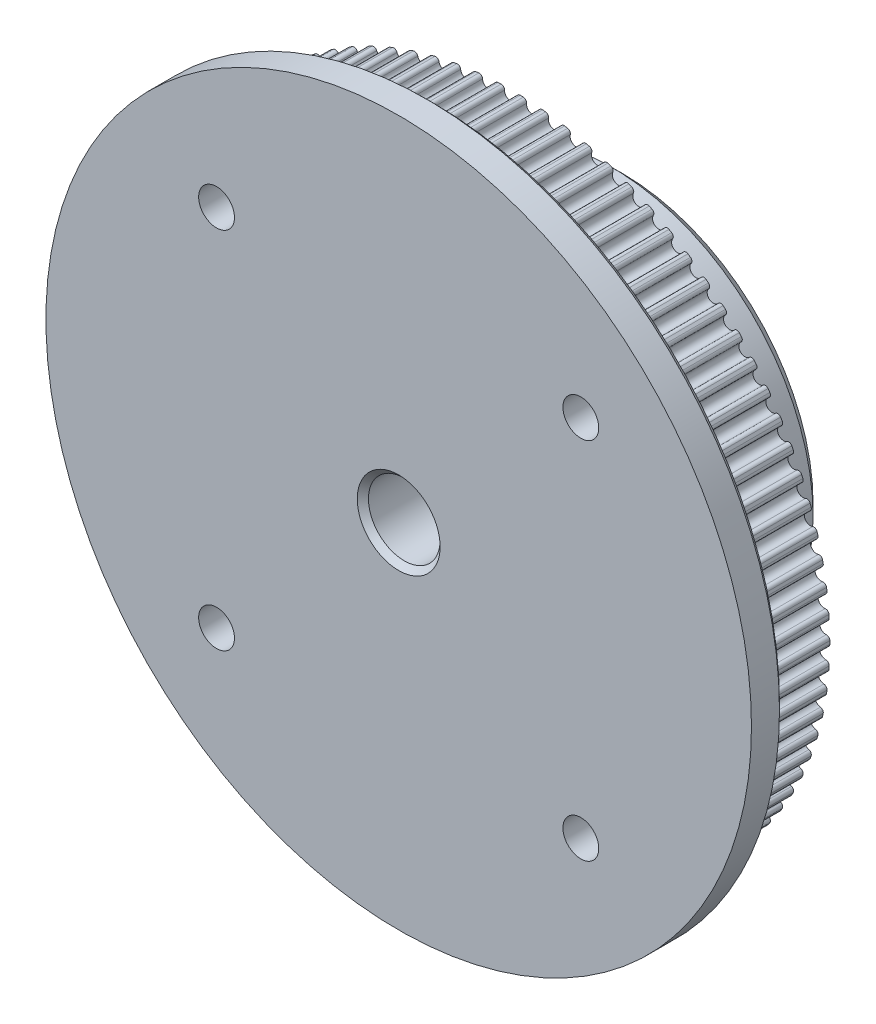
SolidWorks part; units mm, degrees
ref_plane "Спереди" through (0, 0, 0) normal (0, 0, 1) x (1, 0, 0)
ref_plane "Сверху" through (0, 0, 0) normal (0, 1, 0) x (1, 0, 0)
ref_plane "Справа" through (0, 0, 0) normal (1, 0, 0) x (0, 0, -1)
sketch "Эскиз2" plane through (0, 0, 0) normal (1, 0, 0) x (0, 0, -1)
  line L0 (0, 0) -> (0, 31.5)
  line L1 (0, 31.5) -> (3, 31.5)
  line L2 (3, 31.5) -> (3, 28.5)
  line L3 (3, 28.5) -> (10, 28.5)
  line L4 (0, 0) -> (10, 0)
  line L5 (10, 28.5) -> (10, 0)
  dimension "D1" = 3
  dimension "D2" = 7
  dimension "D3" = 28.5
  dimension "D4" = 3
revolve "Повернуть1" add sketch "Эскиз2" angle 360 about L4
sketch "Эскиз5" plane through (0, 0, 0) normal (0, 0, 1) x (1, 0, 0)
  line L1 (0, 0) -> (28.5, 0) construction
  circle A1 centre (0, 0) radius 28.5 construction
  circle A3 centre (0, 0) radius 28.5 construction
sketch "Эскиз7" plane through (0, 0, -10) normal (0, 0, -1) x (-1, 0, 0)
  line L0 (0, 0) -> (0, 28.5) construction
  line L1 (-1.9636, 28.0814) -> (0, 0) construction
  circle A0 centre (0, 0) radius 28.5 construction
  circle A1 centre (0, 28.15) radius 0.55
  circle A2 centre (0, 0) radius 28.5 construction
  circle A3 centre (0, 0) radius 28.5 construction
  circle A4 centre (1.9636, 28.0814) radius 0.55
  circle A5 centre (3.9177, 27.876) radius 0.55
  circle A6 centre (5.8527, 27.5349) radius 0.55
  circle A7 centre (7.7592, 27.0595) radius 0.55
  circle A8 centre (9.6279, 26.4523) radius 0.55
  circle A9 centre (11.4496, 25.7163) radius 0.55
  circle A10 centre (13.2156, 24.855) radius 0.55
  circle A11 centre (14.9172, 23.8726) radius 0.55
  circle A12 centre (16.5462, 22.7738) radius 0.55
  circle A13 centre (18.0945, 21.5642) radius 0.55
  circle A14 centre (19.5546, 20.2494) radius 0.55
  circle A15 centre (20.9195, 18.836) radius 0.55
  circle A16 centre (22.1825, 17.3309) radius 0.55
  circle A17 centre (23.3374, 15.7413) radius 0.55
  circle A18 centre (24.3786, 14.075) radius 0.55
  circle A19 centre (25.3011, 12.3401) radius 0.55
  circle A20 centre (26.1002, 10.5452) radius 0.55
  circle A21 centre (26.7722, 8.6988) radius 0.55
  circle A22 centre (27.3138, 6.8101) radius 0.55
  circle A23 centre (27.7223, 4.8882) radius 0.55
  circle A24 centre (27.9958, 2.9425) radius 0.55
  circle A25 centre (28.1329, 0.9824) radius 0.55
  circle A26 centre (28.1329, -0.9824) radius 0.55
  circle A27 centre (27.9958, -2.9425) radius 0.55
  circle A28 centre (27.7223, -4.8882) radius 0.55
  circle A29 centre (27.3138, -6.8101) radius 0.55
  circle A30 centre (26.7722, -8.6988) radius 0.55
  circle A31 centre (26.1002, -10.5452) radius 0.55
  circle A32 centre (25.3011, -12.3401) radius 0.55
  circle A33 centre (24.3786, -14.075) radius 0.55
  circle A34 centre (23.3374, -15.7413) radius 0.55
  circle A35 centre (22.1825, -17.3309) radius 0.55
  circle A36 centre (20.9195, -18.836) radius 0.55
  circle A37 centre (19.5546, -20.2494) radius 0.55
  circle A38 centre (18.0945, -21.5642) radius 0.55
  circle A39 centre (16.5462, -22.7738) radius 0.55
  circle A40 centre (14.9172, -23.8726) radius 0.55
  circle A41 centre (13.2156, -24.855) radius 0.55
  circle A42 centre (11.4496, -25.7163) radius 0.55
  circle A43 centre (9.6279, -26.4523) radius 0.55
  circle A44 centre (7.7592, -27.0595) radius 0.55
  circle A45 centre (5.8527, -27.5349) radius 0.55
  circle A46 centre (3.9177, -27.876) radius 0.55
  circle A47 centre (1.9636, -28.0814) radius 0.55
  circle A48 centre (0, -28.15) radius 0.55
  circle A49 centre (-1.9636, -28.0814) radius 0.55
  circle A50 centre (-3.9177, -27.876) radius 0.55
  circle A51 centre (-5.8527, -27.5349) radius 0.55
  circle A52 centre (-7.7592, -27.0595) radius 0.55
  circle A53 centre (-9.6279, -26.4523) radius 0.55
  circle A54 centre (-11.4496, -25.7163) radius 0.55
  circle A55 centre (-13.2156, -24.855) radius 0.55
  circle A56 centre (-14.9172, -23.8726) radius 0.55
  circle A57 centre (-16.5462, -22.7738) radius 0.55
  circle A58 centre (-18.0945, -21.5642) radius 0.55
  circle A59 centre (-19.5546, -20.2494) radius 0.55
  circle A60 centre (-20.9195, -18.836) radius 0.55
  circle A61 centre (-22.1825, -17.3309) radius 0.55
  circle A62 centre (-23.3374, -15.7413) radius 0.55
  circle A63 centre (-24.3786, -14.075) radius 0.55
  circle A64 centre (-25.3011, -12.3401) radius 0.55
  circle A65 centre (-26.1002, -10.5452) radius 0.55
  circle A66 centre (-26.7722, -8.6988) radius 0.55
  circle A67 centre (-27.3138, -6.8101) radius 0.55
  circle A68 centre (-27.7223, -4.8882) radius 0.55
  circle A69 centre (-27.9958, -2.9425) radius 0.55
  circle A70 centre (-28.1329, -0.9824) radius 0.55
  circle A71 centre (-28.1329, 0.9824) radius 0.55
  circle A72 centre (-27.9958, 2.9425) radius 0.55
  circle A73 centre (-27.7223, 4.8882) radius 0.55
  circle A74 centre (-27.3138, 6.8101) radius 0.55
  circle A75 centre (-26.7722, 8.6988) radius 0.55
  circle A76 centre (-26.1002, 10.5452) radius 0.55
  circle A77 centre (-25.3011, 12.3401) radius 0.55
  circle A78 centre (-24.3786, 14.075) radius 0.55
  circle A79 centre (-23.3374, 15.7413) radius 0.55
  circle A80 centre (-22.1825, 17.3309) radius 0.55
  circle A81 centre (-20.9195, 18.836) radius 0.55
  circle A82 centre (-19.5546, 20.2494) radius 0.55
  circle A83 centre (-18.0945, 21.5642) radius 0.55
  circle A84 centre (-16.5462, 22.7738) radius 0.55
  circle A85 centre (-14.9172, 23.8726) radius 0.55
  circle A86 centre (-13.2156, 24.855) radius 0.55
  circle A87 centre (-11.4496, 25.7163) radius 0.55
  circle A88 centre (-9.6279, 26.4523) radius 0.55
  circle A89 centre (-7.7592, 27.0595) radius 0.55
  circle A90 centre (-5.8527, 27.5349) radius 0.55
  circle A91 centre (-3.9177, 27.876) radius 0.55
  circle A92 centre (-1.9636, 28.0814) radius 0.55
  circle A93 centre (0, 0) radius 28.15 construction
  point P190 (0, 0)
  dimension "D1" = 1.1
  dimension "D2" = 0.35
  dimension "D5" = 1.1
  dimension "D6" = 1.9636
  dimension "D4" = 4
  dimension "D3" = 90
extrude "Вырез-Вытянуть1" cut sketch "Эскиз7" against normal up to surface (7 mm away) up to face at (31.5, 0, -3)
ref_axis "Ось1" through (0, 0, -18.7751) along (0, 0, 1)
sketch "Эскиз11" plane through (0, 0, -10) normal (0, 0, -1) x (-1, 0, 0)
  arc A0 (-2.4137, 28.3976) -> (-1.562, 28.4572) centre (-1.9636, 28.0814) ccw construction
  arc A1 (-0.4269, 28.4968) -> (0.4269, 28.4968) centre (0, 28.15) ccw construction
  arc A2 (-2.4137, 28.3976) -> (-1.4172, 28.1438) centre (-1.9636, 28.0814) ccw construction
  arc A3 (-0.5495, 28.1741) -> (0.4269, 28.4968) centre (0, 28.15) ccw construction
  circle A4 centre (0, 0) radius 28.5 construction
  arc A5 (-2.4137, 28.3976) -> (0.4269, 28.4968) centre (0, 0) ccw construction
  arc A6 (-0.8582, 28.4871) -> (-1.131, 28.4775) centre (0, 0) ccw construction
  arc A7 (-0.8582, 28.4871) -> (-0.5495, 28.1741) centre (-0.8492, 28.1872) cw construction
  arc A8 (-1.131, 28.4775) -> (-1.4172, 28.1438) centre (-1.1191, 28.1778) ccw construction
  dimension "D1" = 0.3
sketch "Эскиз12" plane through (0, 0, -10) normal (0, 0, -1) x (-1, 0, 0)
  arc A0 (-0.5495, 28.1741) -> (-0.8582, 28.4871) centre (-0.8492, 28.1872) ccw construction
  arc A1 (-1.131, 28.4775) -> (-1.4172, 28.1438) centre (-1.1191, 28.1778) ccw construction
  arc A2 (-0.4269, 28.4968) -> (0.4269, 28.4968) centre (0, 28.15) ccw construction
  arc A3 (-2.4137, 28.3976) -> (-1.562, 28.4572) centre (-1.9636, 28.0814) ccw construction
  circle A4 centre (0, 0) radius 28.5 construction
  arc A5 (-0.5495, 28.1741) -> (-0.8582, 28.4871) centre (-0.8492, 28.1872) ccw
  arc A6 (-1.131, 28.4775) -> (-1.4172, 28.1438) centre (-1.1191, 28.1778) ccw
  arc A7 (-0.4269, 28.4968) -> (-0.5495, 28.1741) centre (0, 28.15) ccw
  arc A8 (-1.4172, 28.1438) -> (-1.562, 28.4572) centre (-1.9636, 28.0814) ccw
  arc A9 (-0.4269, 28.4968) -> (-0.8582, 28.4871) centre (0, 0) ccw
  arc A10 (-1.131, 28.4775) -> (-1.562, 28.4572) centre (0, 0) ccw
extrude "Вырез-Вытянуть3" cut sketch "Эскиз12" against normal up to surface (7 mm away) up to face at (31.5, 0, -3)
pattern_circular "Круговой массив11" count 90 over 360 about axis through (0, 0, -18.7751) along (0, 0, 1) of "Вырез-Вытянуть3"
sketch "Эскиз13" plane through (0, 0, -10) normal (0, 0, -1) x (-1, 0, 0)
  circle A1 centre (0, 0) radius 18
  dimension "D1" = 36
extrude "Бобышка-Вытянуть1" add sketch "Эскиз13" along normal blind 10
chamfer "Фаска1" distance 1 angle 45 1 edges at (18, 0, -10)
chamfer "Фаска2" distance 1 angle 45 1 edges at (-18, 0, -20)
chamfer "Фаска4" distance 0.5 angle 45 1 edges at (31.5, 0, -3)
sketch "Эскиз14" plane through (0, 0, -20) normal (0, 0, -1) x (-1, 0, 0)
  circle A0 centre (0, 0) radius 3.2
  dimension "D1" = 6.4
extrude "Вырез-Вытянуть4" cut sketch "Эскиз14" against normal through all
chamfer "Фаска5" distance 0.5 angle 45 1 edges at (-3.2, 0, 0)
chamfer "Фаска6" distance 0.5 angle 45 1 edges at (-3.2, 0, -20)
ref_plane "Плоскость1" through (0, 0, 0) normal (0, -1, 0) x (1, 0, 0)
ref_plane "Плоскость2" through (0, 18, 0) normal (0, 1, 0) x (1, 0, 0)
sketch "Эскиз16" plane through (0, 18, 0) normal (0, 1, 0) x (1, 0, 0)
  line L0 (19, 10) -> (-19, 10) construction
  line L1 (19, 10) -> (-19, 10) construction
  line L2 (17, 20) -> (-17, 20) construction
  line L3 (17, 20) -> (-17, 20) construction
  line L4 (0, 20) -> (0, 10) construction
  circle A0 centre (0, 17) radius 1.2
  dimension "D1" = 2.4
  dimension "D2" = 3
extrude "Вырез-Вытянуть5" cut sketch "Эскиз16" against normal up to surface (14.8 mm away) up to face at (-3.2, 0, -19.5)
pattern_circular "Круговой массив12" count 4 over 360 about axis through (0, 0, -18.7751) along (0, 0, 1) of "Вырез-Вытянуть5"
sketch "Эскиз17" plane through (0, 0, -10) normal (0, 0, -1) x (-1, 0, 0)
  circle A0 centre (-16.2635, 16.2635) radius 1.6 construction
  circle A1 centre (-16.2635, 16.2635) radius 1.6
  circle A2 centre (16.2635, 16.2635) radius 1.6 construction
  circle A3 centre (16.2635, 16.2635) radius 1.6
  circle A4 centre (16.2635, -16.2635) radius 1.6 construction
  circle A5 centre (16.2635, -16.2635) radius 1.6
  circle A6 centre (-16.2635, -16.2635) radius 1.6 construction
  circle A7 centre (-16.2635, -16.2635) radius 1.6
extrude "Вырез-Вытянуть6" cut sketch "Эскиз17" against normal through all
